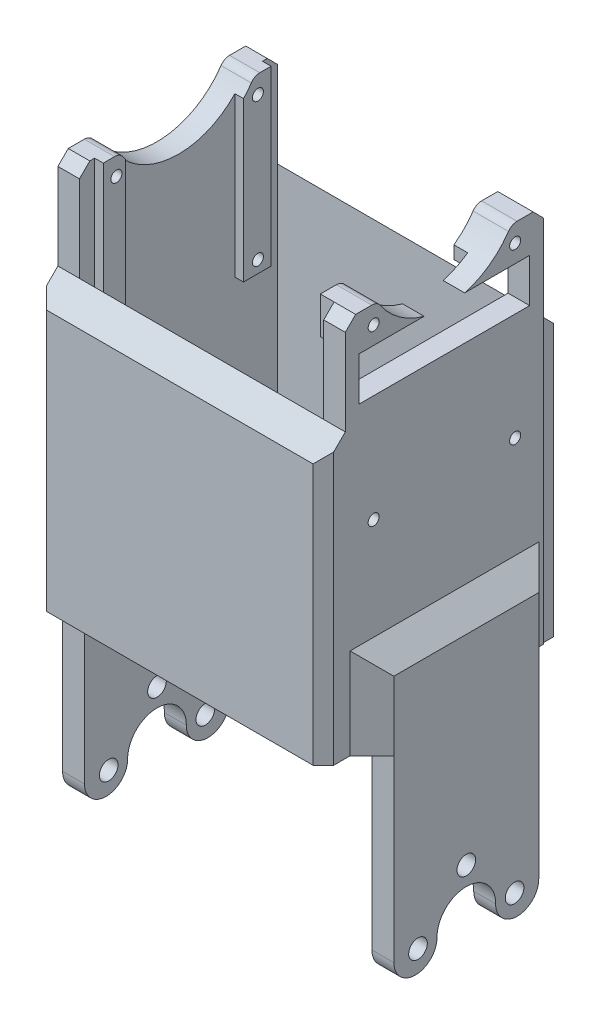
SolidWorks part; units mm, degrees
material "PLA"
ref_plane "Front Plane" through (0, 0, 0) normal (0, 0, 1) x (1, 0, 0)
ref_plane "Top Plane" through (0, 0, 0) normal (0, 1, 0) x (1, 0, 0)
ref_plane "Right Plane" through (0, 0, 0) normal (1, 0, 0) x (0, 0, -1)
sketch "Sketch1" plane through (0, 0, 0) normal (0, 0, 1) x (1, 0, 0)
  line L0 (0, 0) -> (35.4, 0)
  line L1 (35.4, 0) -> (35.4, 51.875)
  line L2 (0, 0) -> (-3.125, 0) construction
  line L3 (35.4, 0) -> (38.525, 0) construction
  line L4 (-3.125, -3.125) -> (38.525, -3.125)
  line L5 (38.525, -3.125) -> (38.525, 51.875)
  line L6 (-3.125, -3.125) -> (-3.125, 51.875)
  line L7 (0, 0) -> (0, 51.875)
  line L8 (0, 51.875) -> (-3.125, 51.875)
  line L9 (35.4, 51.875) -> (38.525, 51.875)
  dimension "D1" = 35.4
  dimension "D2" = 3.125
  dimension "D3" = 3.125
  dimension "D4" = 3.125
  dimension "D5" = 55
  dimension "D6" = 55
extrude "Boss-Extrude1" add sketch "Sketch1" along normal blind 28.72
sketch "Sketch2" plane through (38.525, 0, 0) normal (1, 0, 0) x (0, 0, -1)
  line L0 (-28.72, 46.285) -> (0, 46.285) construction
  line L1 (-28.72, -3.125) -> (-28.72, 51.875) construction
  line L2 (0, -3.125) -> (0, 51.875) construction
  line L3 (-28.72, 51.875) -> (0, 51.875) construction
  line L4 (-14.36, 46.285) -> (-14.36, 57.485) construction
  circle A0 centre (-14.36, 57.485) radius 11.2
  dimension "D1" = 5.59
  dimension "D2" = 11.2
extrude "Cut-Extrude1" cut sketch "Sketch2" against normal through all
fillet "Fillet2" radius 1.5 4 edges at (-1.5625, 51.875, 24.0537) (-1.5625, 51.875, 4.6663) (36.9625, 51.875, 4.6663) (36.9625, 51.875, 24.0537)
sketch "Sketch3" plane through (0, 0, 0) normal (0, 0, -1) x (-1, 0, 0)
  line L1 (-38.325, 37.875) -> (3.125, 37.875)
  line L2 (-38.325, 37.875) -> (-38.325, -3.125)
  line L3 (-38.325, -3.125) -> (3.125, -3.125)
  line L4 (3.125, 37.875) -> (3.125, -3.125)
extrude "Boss-Extrude2" add sketch "Sketch3" along normal blind 3.175
sketch "Sketch4" plane through (0, 0, 28.72) normal (0, 0, 1) x (1, 0, 0)
  line L1 (-3.125, 37.875) -> (38.525, 37.875)
  line L2 (-3.125, 37.875) -> (-3.125, -3.125)
  line L3 (-3.125, -3.125) -> (38.525, -3.125)
  line L4 (38.525, 37.875) -> (38.525, -3.125)
extrude "Boss-Extrude3" add sketch "Sketch4" along normal blind 3.175
chamfer "Chamfer1" distance 3.175 angle 45 2 edges at (17.6, 37.875, -3.175) (17.7, 37.875, 31.895)
chamfer "Chamfer2" distance 1.5 angle 45 4 edges at (-1.5625, 51.875, 0) (36.9625, 51.875, 0) (-1.5625, 51.875, 28.72) (36.9625, 51.875, 28.72)
chamfer "Chamfer3" distance 1.5 angle 45 4 edges at (-3.125, 15.7875, -3.175) (38.325, 15.7875, -3.175) (38.525, 15.7875, 31.895) (-3.125, 15.7875, 31.895)
sketch "Sketch5" plane through (0, 0, 0) normal (1, 0, 0) x (0, 0, -1)
  line L0 (-3.8368, 51.875) -> (-1.5, 51.875) construction
  line L2 (-2.2006, 51.875) -> (-2.2006, 26.7908)
  line L3 (-2.2006, 26.7908) -> (-6.2006, 26.7908)
  line L4 (-6.2006, 49.8127) -> (-6.2006, 26.7908)
  line L6 (-26.5194, 51.875) -> (-26.5194, 26.7908)
  line L7 (-26.5194, 26.7908) -> (-23.7797, 26.7908)
  line L8 (-23.7797, 51.4262) -> (-23.7797, 51.391)
  line L9 (-27.22, 51.875) -> (-24.8832, 51.875) construction
  line L10 (-3.8368, 51.875) -> (-2.2006, 51.875)
  line L11 (-26.5194, 51.875) -> (-24.8832, 51.875)
  line L12 (-23.7797, 26.7908) -> (-23.2826, 26.7908)
  line L13 (-23.2826, 26.7908) -> (-23.2826, 50.7154)
  circle A0 centre (-24.61, 49.2608) radius 0.8
  circle A1 centre (-24.61, 28.5608) radius 0.8
  circle A2 centre (-4.11, 28.5608) radius 0.8
  circle A3 centre (-4.11, 49.2608) radius 0.8
  arc A4 (-3.8368, 51.875) -> (-5.0797, 51.2148) centre (-3.8368, 50.375) ccw construction
  arc A5 (-23.6403, 51.2148) -> (-5.0797, 51.2148) centre (-14.36, 57.485) ccw construction
  arc A6 (-23.6403, 51.2148) -> (-24.8832, 51.875) centre (-24.8832, 50.375) ccw construction
  arc A7 (-3.8368, 51.875) -> (-5.0797, 51.2148) centre (-3.8368, 50.375) ccw
  arc A8 (-23.6403, 51.2148) -> (-23.7797, 51.4262) centre (-14.36, 57.485) ccw
  arc A9 (-23.6403, 51.2148) -> (-24.8832, 51.875) centre (-24.8832, 50.375) ccw
  arc A10 (-6.2006, 49.8127) -> (-5.0797, 51.2148) centre (-14.36, 57.485) ccw
  line M8 (-1.5, 51.875) -> (-3.8368, 51.875)
  arc M9 (-3.8368, 51.875) -> (-5.0797, 51.2148) centre (-3.8368, 50.375) ccw
  arc M10 (-5.0797, 51.2148) -> (-23.6403, 51.2148) centre (-14.36, 57.485) cw
  arc M11 (-23.6403, 51.2148) -> (-24.8832, 51.875) centre (-24.8832, 50.375) ccw
  line M12 (-24.8832, 51.875) -> (-27.22, 51.875)
extrude "Boss-Extrude4" add sketch "Sketch5" along normal blind 1.25 contours L4 L3 L2 A3 A2 M10 M8 M9 | L8 L6 L7 A1 A0 M11 M12 region at (0, 39.1233, 4.1775) region at (0, 39.2642, 24.9256)
sketch "Sketch6" plane through (0, 0, 0) normal (1, 0, 0) x (0, 0, -1)
  circle A0 centre (-24.61, 49.2608) radius 0.8
  circle A1 centre (-24.61, 28.5608) radius 0.8
  circle A2 centre (-4.11, 28.5608) radius 0.8
  circle A3 centre (-4.11, 49.2608) radius 0.8
extrude "Cut-Extrude2" cut sketch "Sketch6" against normal up to next
sketch "Sketch7" plane through (0, -3.125, 0) normal (0, -1, 0) x (1, 0, 0)
  line L0 (11.7, 22.36) -> (23.7, 22.36) construction
  line L1 (23.7, 22.36) -> (23.7, 6.36) construction
  line L2 (23.7, 6.36) -> (11.7, 6.36) construction
  line L3 (11.7, 6.36) -> (11.7, 22.36) construction
  line L6 (-3.125, 30.395) -> (-3.125, -1.675) construction
  line L7 (-1.625, 31.895) -> (37.025, 31.895) construction
  circle A0 centre (11.7, 22.36) radius 1.35
  circle A1 centre (23.7, 22.36) radius 1.35
  circle A2 centre (23.7, 6.36) radius 1.35
  circle A3 centre (11.7, 6.36) radius 1.35
  dimension "D1" = 2.7
  dimension "D2" = 2.7
  dimension "D3" = 2.7
  dimension "D4" = 2.7
  dimension "D5" = 14.825
  dimension "D6" = 9.535
extrude "Cut-Extrude3" cut sketch "Sketch7" against normal up to next
sketch "Sketch8" plane through (35.4, 0, 0) normal (-1, 0, 0) x (0, 0, 1)
  line L0 (7.86, 48.7133) -> (7.86, 45.9108) construction
  line L1 (1.5, 51.875) -> (5.0709, 51.875)
  line L2 (1.5, 51.875) -> (1.5, 46.5164)
  line L3 (1.5, 46.5164) -> (7.86, 46.5164)
  line L4 (7.86, 48.7133) -> (7.86, 46.5164)
  line L5 (20.86, 45.9108) -> (20.86, 48.7133) construction
  line L6 (20.86, 46.5164) -> (27.22, 46.5164)
  line L7 (20.86, 46.5164) -> (20.86, 48.7133)
  line L8 (23.6491, 51.875) -> (27.22, 51.875)
  line L9 (27.22, 46.5164) -> (27.22, 51.875)
  line L10 (28.72, 0) -> (28.72, 37.875) construction
  line L11 (28.72, 27.0608) -> (0, 27.0608)
  line L12 (28.72, 27.0608) -> (28.72, 22.5608)
  line L13 (28.72, 22.5608) -> (0, 22.5608)
  line L14 (0, 27.0608) -> (0, 22.5608)
  circle A0 centre (24.61, 49.2608) radius 0.8
  circle A1 centre (4.11, 49.2608) radius 0.8
  circle A2 centre (4.11, 24.8108) radius 0.8
  circle A3 centre (24.61, 24.735) radius 0.8758
  arc A4 (5.0077, 51.9796) -> (7.7768, 48.8846) centre (14.36, 57.5608) ccw construction
  arc A5 (5.0709, 51.875) -> (7.7768, 48.8846) centre (14.36, 57.5608) ccw
  arc A6 (20.9432, 48.8846) -> (23.7123, 51.9796) centre (14.36, 57.5608) ccw construction
  arc A7 (20.9432, 48.8846) -> (23.6491, 51.875) centre (14.36, 57.5608) ccw
  spline S0 degree 3 poles (-1990.0282, 140.523) (-63.2874, 38.9164) (7.1505, 51.8916) (8.5344, 45.7425) (-54.2619, 48.1267) (797.0615, -1788.4088) knots -94.086847 -94.086847 -94.086847 -94.086847 0.333333 0.666667 91.791331 91.791331 91.791331 91.791331 weights 1 1 1 1 1 1 only from (7.8374, 48.8108) to (7.86, 48.7133) construction
  spline S1 degree 3 poles (-490.8158, 1985.2839) (-30.2177, -10.261) (5.7924, 51.2853) (9.6673, 46.6143) (-37.1403, 7.4582) (460.9115, -1898.6662) knots -96.396237 -96.396237 -96.396237 -96.396237 0.333333 0.666667 89.616596 89.616596 89.616596 89.616596 weights 1 1 1 1 1 1 only from (7.7768, 48.8846) to (7.8374, 48.8108) construction
  spline S2 degree 3 poles (7.8374, 48.8108) (7.8425, 48.8003) (7.851, 48.7791) (7.8584, 48.746) (7.86, 48.7242) (7.86, 48.7133) knots 0 0 0 0 0.333333 0.666667 1 1 1 1 weights 1 1 1 1 1 1
  spline S3 degree 3 poles (7.7768, 48.8846) (7.785, 48.8784) (7.8005, 48.8647) (7.8213, 48.8396) (7.8325, 48.8208) (7.8374, 48.8108) knots 0 0 0 0 0.333333 0.666667 1 1 1 1 weights 1 1 1 1 1 1
  spline S4 degree 3 poles (356.7329, 2019.8863) (65.3071, 28.7044) (19.6993, 46.3936) (21.999, 51.095) (61.1419, 27.6757) (-1071.4379, -1626.044) knots -39.976297 -39.976297 -39.976297 -39.976297 0.341381 0.67758 38.768425 38.768425 38.768425 38.768425 weights 1 1 1 1 1 1 only from (20.86, 48.7133) to (20.9432, 48.8846) construction
  spline S5 degree 3 poles (20.86, 48.7133) (20.86, 48.7357) (20.8668, 48.7804) (20.896, 48.8401) (20.9264, 48.8718) (20.9432, 48.8846) knots 0 0 0 0 0.341381 0.67758 1 1 1 1 weights 1 1 1 1 1 1
  point P42 (0, 24.8108)
  line M9 (0, 37.875) -> (0, 0)
  line M11 (28.72, 0) -> (28.72, 37.875)
  line M14 (27.22, 51.875) -> (24.8832, 51.875)
  arc M15 (24.8832, 51.875) -> (23.6403, 51.2148) centre (24.8832, 50.375) ccw
  arc M16 (23.6403, 51.2148) -> (5.0797, 51.2148) centre (14.36, 57.485) cw
  arc M17 (5.0797, 51.2148) -> (3.8368, 51.875) centre (3.8368, 50.375) ccw
  line M18 (3.8368, 51.875) -> (1.5, 51.875)
  dimension "D1" = 4.5
extrude "Boss-Extrude5" add sketch "Sketch8" along normal blind 2 contours L6 L9 L7 A0 M14 M15 M16 | L4 L2 L3 A1 M16 M17 M18 | L13 L11 A3 A2 M11 M9 region at (35.4, 49.6068, 22.4374) region at (35.4, 51.7918, 2.6684) region at (35.4, 24.8122, 14.3273)
sketch "Sketch9" plane through (35.4, 0, 0) normal (-1, 0, 0) x (0, 0, 1)
  line L0 (24.61, 50.0607) -> (24.61, 48.4608) construction
  line L1 (4.11, 50.0607) -> (4.11, 48.4608) construction
  line L2 (4.11, 25.6107) -> (4.11, 24.0108) construction
  line L3 (24.61, 25.6107) -> (24.61, 24.0108) construction
  line L4 (26.72, 24.4506) -> (26.72, 51.0993) construction
  line L5 (26.72, 46.6769) -> (2, 46.6769)
  line L6 (26.72, 46.6769) -> (26.72, 40.3691)
  line L7 (26.72, 40.3691) -> (2, 40.3691)
  line L8 (2, 46.6769) -> (2, 40.3691)
  line L9 (2, 51.0993) -> (2, 24.4506) construction
  circle A0 centre (24.61, 24.8107) radius 0.8
  circle A1 centre (4.11, 24.8107) radius 0.8
  circle A2 centre (4.11, 49.2607) radius 0.8
  circle A3 centre (24.61, 49.2607) radius 0.8
extrude "Cut-Extrude4" cut sketch "Sketch9" against normal up to next
sketch "Sketch10" plane through (-3.125, 0, 0) normal (-1, 0, 0) x (0, 0, 1)
  line L0 (3.86, -9.6264) -> (3.86, 3.5377) construction
  line L1 (3.86, -29.0691) -> (3.86, -5.125) construction
  line L2 (24.86, -9.6264) -> (24.86, 3.5377) construction
  line L3 (24.86, -29.0691) -> (24.86, -5.125) construction
  line L4 (30.395, -3.125) -> (-1.675, -3.125) construction
  line L5 (3.86, 6.875) -> (24.86, 6.875)
  line L6 (3.86, 6.875) -> (3.86, -29.0691)
  line L8 (24.86, 6.875) -> (24.86, -29.0691)
  spline S6 degree 3 poles (18.6098, -29.0691) (18.6098, -35.3193) (24.86, -35.3193) (24.86, -29.0691) knots 0 0 0 0 1 1 1 1 weights 1 0.333333 0.333333 1 construction
  spline S7 degree 3 poles (10.1102, -29.0691) (10.0842, -26.5591) (11.8499, -24.775) (14.36, -24.775) (16.8701, -24.775) (18.6358, -26.5591) (18.6098, -29.0691) knots 0 0 0 0 0.5 0.5 0.5 1 1 1 1 weights 1 0.802287 0.802287 1 0.802287 0.802287 1 construction
  spline S8 degree 3 poles (3.86, -29.0691) (3.86, -30.8997) (5.1545, -32.1942) (6.9851, -32.1942) (8.8158, -32.1942) (10.1102, -30.8997) (10.1102, -29.0691) knots 0 0 0 0 0.5 0.5 0.5 1 1 1 1 weights 1 0.804738 0.804738 1 0.804738 0.804738 1 construction
  spline S15 degree 3 poles (18.6098, -29.0691) (18.6098, -35.3193) (24.86, -35.3193) (24.86, -29.0691) knots 0 0 0 0 1 1 1 1 weights 1 0.333333 0.333333 1
  spline S16 degree 3 poles (10.1102, -29.0691) (10.0842, -26.5591) (11.8499, -24.775) (14.36, -24.775) (16.8701, -24.775) (18.6358, -26.5591) (18.6098, -29.0691) knots 0 0 0 0 0.5 0.5 0.5 1 1 1 1 weights 1 0.802287 0.802287 1 0.802287 0.802287 1
  spline S17 degree 3 poles (3.86, -29.0691) (3.86, -30.8997) (5.1545, -32.1942) (6.9851, -32.1942) (8.8158, -32.1942) (10.1102, -30.8997) (10.1102, -29.0691) knots 0 0 0 0 0.5 0.5 0.5 1 1 1 1 weights 1 0.804738 0.804738 1 0.804738 0.804738 1
  dimension "D1" = 10
extrude "Boss-Extrude6" add sketch "Sketch10" along normal blind 3.175
chamfer "Chamfer8" distance 3.175 angle 45 3 edges at (-3.125, 1.875, 3.86) (-3.125, 6.875, 14.36) (-3.125, 1.875, 24.86)
ref_plane "Plane1" through (17.7, 0, 0) normal (1, 0, 0) x (0, 0, -1)
mirror "Mirror2" about plane through (17.7, 0, 0) normal (1, 0, 0) of "Boss-Extrude6"
chamfer "Chamfer9" distance 3.175 angle 45 3 edges at (38.525, 1.875, 24.86) (38.525, 6.875, 14.36) (38.525, 1.875, 3.86)
sketch "Sketch11" plane through (-6.3, 0, 0) normal (-1, 0, 0) x (0, 0, 1)
  line L0 (3.86, -29.0691) -> (24.86, -29.0691) construction
  circle A0 centre (14.36, -29.0691) radius 7 construction
  circle A1 centre (7.36, -29.0691) radius 1.35
  circle A6 centre (14.36, -22.0691) radius 1.35
  circle A7 centre (21.36, -29.0691) radius 1.35
  dimension "D6" = 14
  dimension "D7" = 2.7
extrude "Cut-Extrude5" cut sketch "Sketch11" against normal through all
